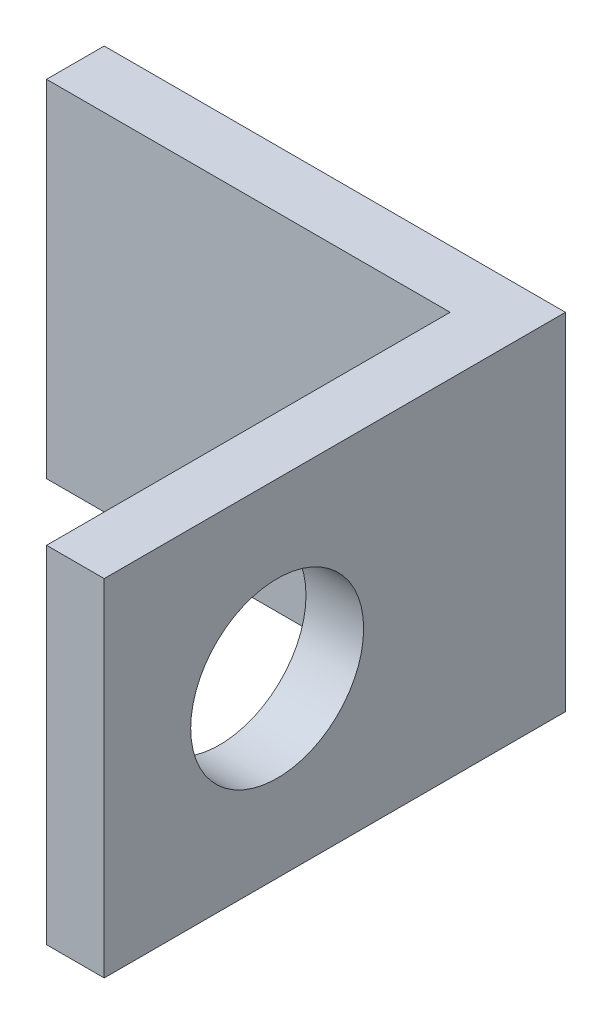
SolidWorks part; units mm, degrees
material "1060 Alloy"
ref_plane "Front" through (0, 0, 0) normal (0, 0, 1) x (1, 0, 0)
ref_plane "Top" through (0, 0, 0) normal (0, 1, 0) x (1, 0, 0)
ref_plane "Right" through (0, 0, 0) normal (1, 0, 0) x (0, 0, -1)
sketch "Sketch1" plane through (0, 0, 0) normal (0, 1, 0) x (1, 0, 0)
  line L0 (0, 0) -> (12.7, 0)
  line L1 (12.7, 0) -> (12.7, -12.7)
  line L2 (12.7, -12.7) -> (11.1125, -12.7)
  line L3 (11.1125, -12.7) -> (11.1125, -1.5875)
  line L4 (11.1125, -1.5875) -> (0, -1.5875)
  line L5 (0, -1.5875) -> (0, 0)
  dimension "D1" = 1.5875
  dimension "D2" = 1.5875
  dimension "D3" = 12.7
  dimension "D4" = 12.7
extrude "Boss-Extrude1" add sketch "Sketch1" along normal blind 9.525
hole_wizard "3/16 (0.1875) Diameter Hole1" positions "Sketch2" profile "Sketch3" hole size "3/16" standard "ANSI Inch" end condition through all
sketch "Sketch2" plane through (11.1125, 0, 0) normal (-1, 0, 0) x (0, 0, 1)
  line L0 (12.7, 9.525) -> (12.7, 0) construction
  point P0 (7.9375, 4.7625)
  point P7 (12.7, 4.7625)
  dimension "D1" = 4.7625
sketch "Sketch3" plane through (11.1125, 4.7625, 7.9375) normal (0, 1, 0) x (0, 0, 1)
  line L0 (0, 0) -> (0, 1.5875)
  line L1 (0, 1.5875) -> (2.3812, 1.5875)
  line L2 (2.3812, 1.5875) -> (2.3812, 0)
  line L5 (2.3812, 0) -> (0, 0)
  line L11 (0, -6.35) -> (0, 107.95) construction
  dimension "Thru Hole Dia." = 4.7625
  dimension "Thru Hole Depth" = 1.5875
